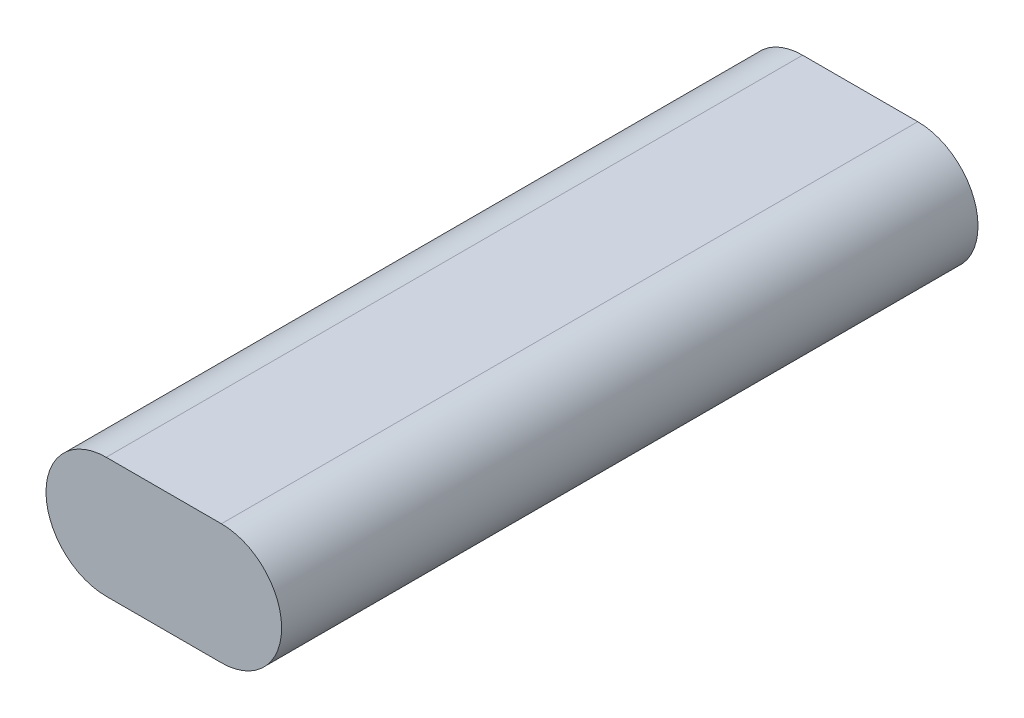
SolidWorks part; units mm, degrees
ref_plane "Plan de face" through (0, 0, 0) normal (0, 0, 1) x (1, 0, 0)
ref_plane "Plan de dessus" through (0, 0, 0) normal (0, 1, 0) x (1, 0, 0)
ref_plane "Plan de droite" through (0, 0, 0) normal (1, 0, 0) x (0, 0, -1)
sketch "Esquisse1" plane through (0, 0, 0) normal (0, 0, 1) x (1, 0, 0)
  line L0 (0, 0) -> (22, 0) construction
  line L1 (0, 11.5) -> (22, 11.5)
  line L2 (0, -11.5) -> (22, -11.5)
  arc A0 (0, 11.5) -> (0, -11.5) centre (0, 0) ccw
  arc A1 (22, -11.5) -> (22, 11.5) centre (22, 0) ccw
  point P3 (11, 0)
  dimension "D1" = 22
  dimension "D2" = 23
extrude "Extrusion1" add sketch "Esquisse1" along normal blind 133
sketch "Esquisse2" plane through (0, 0, 0) normal (0, 0, -1) x (-1, 0, 0)
  line L0 (-22, 5) -> (0, 5)
  line L1 (-22, -5) -> (0, -5)
  arc A0 (0, -5) -> (0, 5) centre (0, 0) ccw
  arc A1 (-22, 5) -> (-22, -5) centre (-22, 0) ccw
  arc A2 (-22, 11.5) -> (-22, -11.5) centre (-22, 0) ccw construction
  dimension "D1" = 10
extrude "Extrusion2" add sketch "Esquisse2" along normal blind 1
chamfer "Chanfrein1" distance 1 angle 45 4 edges at (11, 5, 0) (-5, 0, 0) (27, 0, 0) (11, -5, 0)
sketch "Esquisse3" plane through (0, 0, -1) normal (0, 0, -1) x (-1, 0, 0)
  line L0 (-13, 4) -> (-9, 4)
  line L1 (-9, -4) -> (-13, -4)
  arc A0 (-13, 4) -> (-13, -4) centre (-13, 0) ccw
  arc A1 (-9, -4) -> (-9, 4) centre (-9, 0) ccw
  dimension "D2" = 8
  dimension "D4" = 9
  dimension "D3" = 4
extrude "Extrusion3" add sketch "Esquisse3" along normal blind 3
sketch "Esquisse4" plane through (0, 0, -4) normal (0, 0, -1) x (-1, 0, 0)
  line L0 (-13, 2.5) -> (-9, 2.5)
  line L1 (-9, -2.5) -> (-13, -2.5)
  arc A0 (-9, -2.5) -> (-9, 2.5) centre (-9, 0) ccw
  arc A1 (-13, 2.5) -> (-13, -2.5) centre (-13, 0) ccw
  arc A2 (-13, 4) -> (-13, -4) centre (-13, 0) ccw construction
  arc A3 (-9, -4) -> (-9, 4) centre (-9, 0) ccw construction
  dimension "D1" = 5
  dimension "D2" = 5
extrude "Extrusion4" cut sketch "Esquisse4" against normal blind 10
